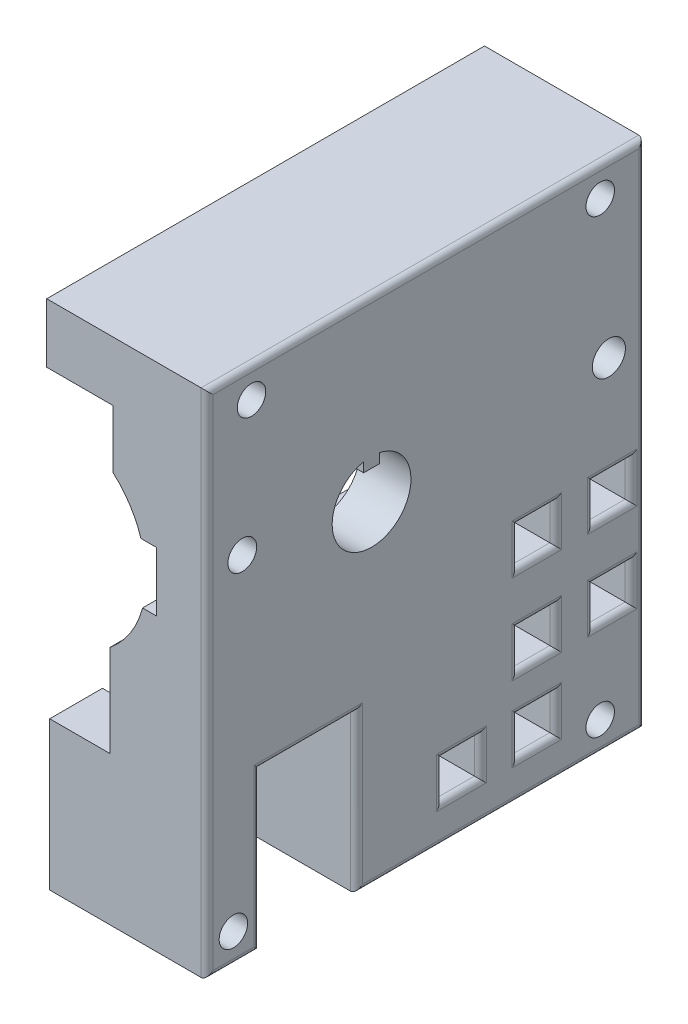
SolidWorks part; units mm, degrees
ref_plane "Front" through (0, 0, 0) normal (0, 0, 1) x (1, 0, 0)
ref_plane "Top" through (0, 0, 0) normal (0, 1, 0) x (1, 0, 0)
ref_plane "Right" through (0, 0, 0) normal (1, 0, 0) x (0, 0, -1)
sketch "Profile" plane through (0, 0, 0) normal (0, 0, 1) x (1, 0, 0)
  line L0 (-6.0107, -58.6279) -> (-6.0107, -33.6279)
  line L1 (-6.0107, -58.6279) -> (20.4893, -58.6279)
  line L2 (-6.5107, 17.4121) -> (-6.5107, 27.4121)
  line L3 (-6.5107, 27.4121) -> (20.4893, 27.4121)
  line L4 (20.4893, -58.6279) -> (20.4893, 27.4121)
  line L5 (-6.0107, -33.6279) -> (4.1393, -33.6279)
  line L6 (4.1393, -33.6279) -> (4.1393, -18.1379)
  line L7 (9.6313, -9.6379) -> (11.9493, -9.6379)
  line L8 (11.9493, -9.6379) -> (11.9493, 0.3621)
  line L9 (9.3593, 0.3621) -> (11.9493, 0.3621)
  line L10 (4.6393, 17.4121) -> (4.6393, 7.6371)
  line L11 (4.6393, 17.4121) -> (-6.5107, 17.4121)
  arc A0 (9.3593, 0.3621) -> (4.6393, 7.6371) centre (-6.1482, -4.5305) ccw
  arc A1 (4.1393, -18.1379) -> (9.6313, -9.6379) centre (-6.0948, -5.5013) ccw
  dimension "D14" = 16.261
  dimension "D17" = 16.261
  dimension "D2" = 10
  dimension "D3" = 2.59
  dimension "D4" = 2.318
  dimension "D5" = 9.775
  dimension "D6" = 11.15
  dimension "D7" = 15.49
  dimension "D8" = 10.15
  dimension "D9" = 25
  dimension "D10" = 26.5
  dimension "D11" = 86.04
  dimension "D12" = 27
  dimension "D13" = 10
  dimension "D15" = 23.99
  dimension "D16" = 5.492
extrude "ProfileExtrude" add sketch "Profile" along normal blind 73.76
sketch "HoseWindow" plane through (20.4893, 0, 0) normal (1, 0, 0) x (0, 0, -1)
  line L0 (-73.76, -58.6279) -> (0, -58.6279) construction
  line L1 (-64.87, -58.6279) -> (-48.58, -58.6279)
  line L2 (-64.87, -58.6279) -> (-64.87, -32.1279)
  line L3 (-64.87, -32.1279) -> (-48.58, -32.1279)
  line L4 (-48.58, -58.6279) -> (-48.58, -32.1279)
  line L5 (-73.76, -58.6279) -> (-73.76, 27.4121) construction
  dimension "D1" = 16.29
  dimension "D2" = 26.5
  dimension "D3" = 8.89
extrude "HoseWindowCut" cut sketch "HoseWindow" against normal through all
sketch "CageScrews" plane through (20.4893, 0, 0) normal (1, 0, 0) x (0, 0, -1)
  line L0 (-73.76, 27.4121) -> (0, 27.4121) construction
  line L1 (-73.76, -58.6279) -> (-73.76, 27.4121) construction
  line L2 (0, -58.6279) -> (0, 27.4121) construction
  line L3 (-48.58, -58.6279) -> (0, -58.6279) construction
  line L4 (-73.76, -58.6279) -> (-64.87, -58.6279) construction
  circle A0 centre (-66.26, 22.4121) radius 2.4
  circle A1 centre (-7.5, 22.4121) radius 2.4
  circle A2 centre (-7.5, -53.6279) radius 2.4
  circle A3 centre (-69.31, -53.6279) radius 2.4
  dimension "D1" = 4.8
  dimension "D2" = 4.8
  dimension "D3" = 4.8
  dimension "D4" = 4.8
  dimension "D5" = 5
  dimension "D6" = 7.5
  dimension "D7" = 7.5
  dimension "D8" = 5
  dimension "D9" = 5
  dimension "D10" = 7.5
  dimension "D11" = 5
  dimension "D12" = 4.45
extrude "CageScrewsCut" cut sketch "CageScrews" against normal through all
sketch "AxleHole" plane through (20.4893, 0, 0) normal (1, 0, 0) x (0, 0, -1)
  line L0 (-46.03, 2.3073) -> (-46.03, -9.2169) construction
  line L1 (-44.699, 2.3073) -> (-47.361, 2.3073)
  line L2 (-47.361, 2.3073) -> (-47.361, 3.9263)
  line L3 (-44.699, 2.3073) -> (-44.699, 3.9263)
  line L4 (-48.58, -58.6279) -> (0, -58.6279) construction
  line L5 (0, -58.6279) -> (0, 27.4121) construction
  arc A0 (-47.361, 3.9263) -> (-44.699, 3.9263) centre (-46.03, -2.5779) ccw
  dimension "D1" = 13.278
  dimension "D2" = 1.619
  dimension "D3" = 1.619
  dimension "D4" = 1.331
  dimension "D5" = 56.05
  dimension "D6" = 46.03
extrude "AxleHoleCut" cut sketch "AxleHole" against normal through all
sketch "SetScrews" plane through (20.4893, 0, 0) normal (1, 0, 0) x (0, 0, -1)
  line L0 (-46.03, -9.2169) -> (-46.03, -2.5779) construction
  circle A0 centre (-67.8072, 0.5449) radius 2.4263
  circle A1 centre (-6.043, -1.5582) radius 2.7888
  arc A3 (-47.361, 3.9263) -> (-44.699, 3.9263) centre (-46.03, -2.5779) ccw construction
  dimension "D1" = 22
  dimension "D2" = 40
extrude "SetScrewsCut" cut sketch "SetScrews" against normal through all
sketch "Sketch1" plane through (20.4893, 0, 0) normal (1, 0, 0) x (0, 0, -1)
  line L0 (-21.35, -45.9279) -> (-21.35, -52.2779)
  line L1 (-21.35, -45.9279) -> (-15, -45.9279)
  line L2 (-21.35, -52.2779) -> (-15, -52.2779)
  line L3 (-15, -45.9279) -> (-15, -52.2779)
  line L4 (0, -58.6279) -> (0, 27.4121) construction
  line L5 (-48.58, -58.6279) -> (0, -58.6279) construction
  line L6 (-34.05, -45.9279) -> (-34.05, -52.2779)
  line L7 (-34.05, -45.9279) -> (-27.7, -45.9279)
  line L8 (-34.05, -52.2779) -> (-27.7, -52.2779)
  line L9 (-27.7, -45.9279) -> (-27.7, -52.2779)
  line L10 (-8.65, -33.2279) -> (-8.65, -39.5779)
  line L11 (-8.65, -33.2279) -> (-2.3, -33.2279)
  line L12 (-8.65, -39.5779) -> (-2.3, -39.5779)
  line L13 (-2.3, -33.2279) -> (-2.3, -39.5779)
  line L14 (-21.35, -33.2279) -> (-21.35, -39.5779)
  line L15 (-21.35, -33.2279) -> (-15, -33.2279)
  line L16 (-21.35, -39.5779) -> (-15, -39.5779)
  line L17 (-15, -33.2279) -> (-15, -39.5779)
  line L18 (-34.05, -33.2279) -> (-34.05, -39.5779) [skipped]
  line L19 (-34.05, -33.2279) -> (-27.7, -33.2279) [skipped]
  line L20 (-34.05, -39.5779) -> (-27.7, -39.5779) [skipped]
  line L21 (-27.7, -33.2279) -> (-27.7, -39.5779) [skipped]
  line L22 (-8.65, -18.2279) -> (-8.65, -24.5779)
  line L23 (-8.65, -18.2279) -> (-2.3, -18.2279)
  line L24 (-8.65, -24.5779) -> (-2.3, -24.5779)
  line L25 (-2.3, -18.2279) -> (-2.3, -24.5779)
  line L26 (-21.35, -18.2279) -> (-21.35, -24.5779)
  line L27 (-21.35, -18.2279) -> (-15, -18.2279)
  line L28 (-21.35, -24.5779) -> (-15, -24.5779)
  line L29 (-15, -18.2279) -> (-15, -24.5779)
  dimension "D1" = 15
  dimension "D2" = 6.35
  dimension "D3" = 6.35
  dimension "D4" = 6.35
  dimension "D5" = 2
  dimension "D6" = 2
  dimension "D7" = 2
  dimension "D8" = 2
extrude "Cut-Extrude1" cut sketch "Sketch1" against normal through all
fillet "Fillet1" radius 1 32 edges at (20.4893, -52.2779, 30.875) (20.4893, -49.1029, 34.05) (20.4893, -45.9279, 30.875) (20.4893, -49.1029, 27.7) (20.4893, -49.1029, 21.35) (20.4893, -52.2779, 18.175) (20.4893, -49.1029, 15) (20.4893, -45.9279, 18.175) (20.4893, -36.4029, 8.65) (20.4893, -39.5779, 5.475) (20.4893, -36.4029, 2.3) (20.4893, -33.2279, 5.475) (20.4893, -36.4029, 21.35) (20.4893, -39.5779, 18.175) (20.4893, -36.4029, 15) (20.4893, -33.2279, 18.175) (20.4893, -21.4029, 21.35) (20.4893, -24.5779, 18.175) (20.4893, -21.4029, 15) (20.4893, -18.2279, 18.175) (20.4893, -21.4029, 8.65) (20.4893, -24.5779, 5.475) (20.4893, -21.4029, 2.3) (20.4893, -18.2279, 5.475) (20.4893, -58.6279, 69.315) (20.4893, -45.3779, 64.87) (20.4893, -32.1279, 56.725) (20.4893, -45.3779, 48.58) (20.4893, -58.6279, 24.29) (20.4893, -15.6079, 0) (20.4893, 27.4121, 36.88) (20.4893, -15.6079, 73.76)
equation "\"BottomEdge\"=26.5mm"
equation "\"TopEdge\"=27mm"
equation "\"TotalHeight\"=86.04mm"
equation "\"TotalLength\"=73.76mm"
equation "\"Screw Clearance\" = 10mm"
equation "\"TopDepth\"= 11.15mm"
equation "\"BottomDepth\"=10.15mm"
equation "\"TopHeight\"=9.775mm"
equation "\"BottomHeight\"=15.49mm"
equation "\"TopChannelDepth\"=2.59mm"
equation "\"BottomChannelDepth\"=2.318mm"
equation "\"ChannelHeight\"=10mm"
equation "\"ChamberRadius\"=16.261mm"
equation "\"ChanRelHeight\"=23.99mm"
equation "\"ChanRelDepth\"=5.492mm"
equation "\"D2@Profile\"= \"ChannelHeight\""
equation "\"D4@Profile\"= \"BottomChannelDepth\""
equation "\"D3@Profile\"= \"TopChannelDepth\""
equation "\"D5@Profile\"= \"TopHeight\""
equation "\"D7@Profile\"= \"BottomHeight\""
equation "\"ScrewClearanceBottom\" = 25mm"
equation "\"D9@Profile\"=\"ScrewClearanceBottom\""
equation "\"D13@Profile\"= \"Screw Clearance\""
equation "\"D8@Profile\"= \"BottomDepth\""
equation "\"D6@Profile\"= \"TopDepth\""
equation "\"D10@Profile\"= \"BottomEdge\""
equation "\"D12@Profile\"= \"TopEdge\""
equation "\"D11@Profile\"= \"TotalHeight\""
equation "\"D15@Profile\"= \"ChanRelHeight\""
equation "\"D16@Profile\"= \"ChanRelDepth\""
equation "\"D17@Profile\"= \"ChamberRadius\""
equation "\"D14@Profile\"= \"ChamberRadius\""
equation "\"D1@ProfileExtrude\"= \"TotalLength\""
equation "\"CageScrewDiameter\"=4.8mm"
equation "\"SetScrewDiameter\"=3.5mm"
equation "\"AxleRadius\"=6.639mm"
equation "\"KeyHeight\"=1.619mm"
equation "\"KeyWidth\"=2.662mm"
equation "\"HoseWindowWidth\"=16.29mm"
equation "\"HoseWindowHeight\"=26.5mm"
equation "\"HoseWindow-Edge\"=8.89mm"
equation "\"CageScrew-VerticalEdge\"=5.0mm"
equation "\"CageScrew-HorizontalEdge\"=7.5mm"
equation "\"CageScrew-HoseCornerScrewEdge\"=4.45mm"
equation "\"Axle-BottomEdge\"=56.05mm"
equation "\"Axle-FrontEdge\"=46.03mm"
equation "\"FrontSetScrew-Axel\"=40mm"
equation "\"D1@HoseWindow\"= \"HoseWindowWidth\""
equation "\"D2@HoseWindow\"= \"HoseWindowHeight\""
equation "\"D3@HoseWindow\"= \"HoseWindow-Edge\""
equation "\"D6@CageScrews\"= \"CageScrew-HorizontalEdge\""
equation "\"D7@CageScrews\"= \"CageScrew-HorizontalEdge\""
equation "\"D10@CageScrews\"= \"CageScrew-HorizontalEdge\""
equation "\"D12@CageScrews\"= \"CageScrew-HoseCornerScrewEdge\""
equation "\"D5@CageScrews\"= \"CageScrew-VerticalEdge\""
equation "\"D8@CageScrews\"= \"CageScrew-VerticalEdge\""
equation "\"D11@CageScrews\"= \"CageScrew-VerticalEdge\""
equation "\"D9@CageScrews\"= \"CageScrew-VerticalEdge\""
equation "\"D1@CageScrews\"= \"CageScrewDiameter\""
equation "\"D2@CageScrews\"= \"CageScrewDiameter\""
equation "\"D4@CageScrews\"= \"CageScrewDiameter\""
equation "\"D3@CageScrews\"= \"CageScrewDiameter\""
equation "\"D1@AxleHole\"= \"AxleRadius\" * 2"
equation "\"D3@AxleHole\"= \"KeyHeight\""
equation "\"D2@AxleHole\"= \"KeyHeight\""
equation "\"D4@AxleHole\"= \"KeyWidth\" / 2"
equation "\"D6@AxleHole\"= \"Axle-FrontEdge\""
equation "\"D5@AxleHole\"= \"Axle-BottomEdge\""
equation "\"D2@SetScrews\"= \"FrontSetScrew-Axel\""
equation "\"BackSetScrew-Axel\"=22mm"
equation "\"D1@SetScrews\"= \"BackSetScrew-Axel\""
equation "\"SlotFront\"=15mm"
equation "\"D1@Sketch1\"=\"SlotFront\""
equation "\"Slot\"=6.35mm"
equation "\"D2@Sketch1\"=\"Slot\""
equation "\"D3@Sketch1\"=\"Slot\""
equation "\"SlotBottom\"=6.35mm"
equation "\"D4@Sketch1\"=\"SlotBottom\""
